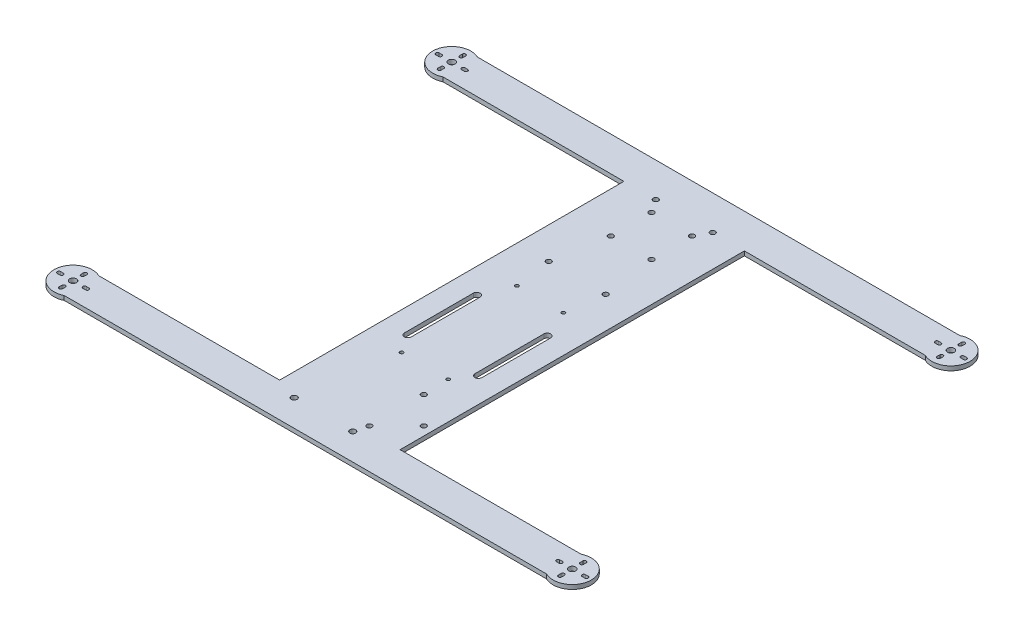
SolidWorks part; units mm, degrees
ref_plane "Front Plane" through (0, 0, 0) normal (0, 0, 1) x (1, 0, 0)
ref_plane "Top Plane" through (0, 0, 0) normal (0, 1, 0) x (1, 0, 0)
ref_plane "Right Plane" through (0, 0, 0) normal (1, 0, 0) x (0, 0, -1)
sketch "Sketch2" plane through (0, 0, 0) normal (0, 1, 0) x (1, 0, 0)
  line L0 (-44.45, 0) -> (44.45, 0) construction
  line L1 (-41.275, 152.4) -> (41.275, 152.4)
  line L2 (-44.45, 149.225) -> (-44.45, -149.225)
  line L3 (-41.275, -152.4) -> (41.275, -152.4)
  line L4 (44.45, 149.225) -> (44.45, -149.225)
  line L5 (0, 152.4) -> (0, -152.4) construction
  arc A0 (-44.45, -149.225) -> (-41.275, -152.4) centre (-41.275, -149.225) ccw
  arc A1 (41.275, -152.4) -> (44.45, -149.225) centre (41.275, -149.225) ccw
  arc A2 (41.275, 152.4) -> (44.45, 149.225) centre (41.275, 149.225) cw
  arc A3 (-41.275, 152.4) -> (-44.45, 149.225) centre (-41.275, 149.225) ccw
  point P8 (0, 0)
  point P13 (-44.45, -152.4)
  point P16 (44.45, -152.4)
  point P21 (-44.45, 152.4)
  dimension "D3" = 3.175
  dimension "D1" = 304.8
  dimension "D2" = 88.9
extrude "Plate Thickness" add sketch "Sketch2" along normal blind 3.175 contours L2 A0 L3 A1 L4 A2 L1 A3
sketch "Sketch10" plane through (0, 3.175, 0) normal (0, 1, 0) x (1, 0, 0)
  line L1 (41.275, 152.4) -> (177.986, 152.4)
  line L2 (41.275, 152.4) -> (41.275, 127)
  line L3 (41.275, 127) -> (177.986, 127)
  line L5 (44.45, 149.225) -> (44.45, -149.225) construction
  line L6 (0, 0) -> (0, 234.1968) construction
  line L7 (0, 0) -> (254.2756, 0) construction
  line L8 (41.275, -127) -> (177.986, -127)
  line L9 (41.275, -152.4) -> (41.275, -127)
  line L10 (41.275, -152.4) -> (177.986, -152.4)
  line L11 (41.275, 152.4) -> (177.986, 152.4)
  line L12 (41.275, 152.4) -> (41.275, 127)
  line L13 (41.275, 127) -> (177.986, 127)
  line L14 (41.275, -127) -> (177.986, -127)
  line L15 (41.275, -152.4) -> (41.275, -127)
  line L16 (41.275, -152.4) -> (177.986, -152.4)
  line L17 (41.275, 152.4) -> (177.986, 152.4)
  line L18 (41.275, 152.4) -> (41.275, 127)
  line L19 (41.275, 127) -> (177.986, 127)
  line L20 (41.275, -127) -> (177.986, -127)
  line L21 (41.275, -152.4) -> (41.275, -127)
  line L22 (41.275, -152.4) -> (177.986, -152.4)
  line L23 (41.275, 152.4) -> (177.986, 152.4)
  line L24 (41.275, 152.4) -> (41.275, 127)
  line L25 (41.275, 127) -> (177.986, 127)
  line L26 (41.275, -127) -> (177.986, -127)
  line L27 (41.275, -152.4) -> (41.275, -127)
  line L28 (41.275, -152.4) -> (177.986, -152.4)
  line L29 (-41.275, -127) -> (-177.986, -127)
  line L30 (-41.275, -152.4) -> (-41.275, -127)
  line L31 (-41.275, -152.4) -> (-177.986, -152.4)
  line L32 (-41.275, 127) -> (-177.986, 127)
  line L33 (-41.275, 152.4) -> (-41.275, 127)
  line L34 (-41.275, 152.4) -> (-177.986, 152.4)
  arc A0 (177.986, 127) -> (177.986, 152.4) centre (184.15, 139.7) ccw
  arc A1 (177.986, -127) -> (177.986, -152.4) centre (184.15, -139.7) cw
  arc A2 (177.986, 127) -> (177.986, 152.4) centre (184.15, 139.7) ccw
  arc A3 (177.986, -127) -> (177.986, -152.4) centre (184.15, -139.7) cw
  arc A4 (177.986, 127) -> (177.986, 152.4) centre (184.15, 139.7) ccw
  arc A5 (177.986, -127) -> (177.986, -152.4) centre (184.15, -139.7) cw
  arc A6 (177.986, 127) -> (177.986, 152.4) centre (184.15, 139.7) ccw
  arc A7 (177.986, -127) -> (177.986, -152.4) centre (184.15, -139.7) cw
  arc A8 (-177.986, -127) -> (-177.986, -152.4) centre (-184.15, -139.7) ccw
  arc A9 (-177.986, 127) -> (-177.986, 152.4) centre (-184.15, 139.7) cw
  point P27 (184.15, 134.2785)
  point P28 (0, 0)
  point P29 (0, 0)
  arc M45 (-41.275, 152.4) -> (-44.45, 149.225) centre (-41.275, 149.225) ccw
  line M46 (-44.45, 149.225) -> (-44.45, -149.225)
  arc M47 (-44.45, -149.225) -> (-41.275, -152.4) centre (-41.275, -149.225) ccw
  arc M49 (41.275, -152.4) -> (44.45, -149.225) centre (41.275, -149.225) ccw
  line M50 (44.45, -149.225) -> (44.45, 149.225)
  arc M51 (44.45, 149.225) -> (41.275, 152.4) centre (41.275, 149.225) ccw
  dimension "D1" = 139.7
  dimension "D2" = 25.4
extrude "Boss-Extrude1" add sketch "Sketch10" against normal up to surface (3.175 mm away) contours A9 L32 L34 M46 M45 | L3 A0 L1 M51 M50 | A1 L8 L10 M50 M49 | L29 A8 L31 M47 M46 region at (120.5918, 3.175, 139.7067) region at (120.5918, 3.175, -139.7067) region at (-120.5918, 3.175, -139.7067) region at (-120.5918, 3.175, 139.7067) up to face at (0, 0, 0)
sketch "Sketch3" plane through (0, 3.175, 0) normal (0, 1, 0) x (1, 0, 0)
  line L0 (-44.45, 127) -> (-44.45, -127) construction
  line L1 (-177.986, 152.4) -> (177.986, 152.4) construction
  line L4 (0, 152.4) -> (0, -152.4) construction
  line L5 (-177.986, -152.4) -> (177.986, -152.4) construction
  circle A0 centre (-38.1, 146.05) radius 2.159
  circle A1 centre (-38.1, 79.375) radius 2.159
  circle A2 centre (-38.1, -66.675) radius 2.159
  circle A3 centre (-38.1, -133.35) radius 2.159
  circle A4 centre (38.1, -133.35) radius 2.159
  circle A5 centre (38.1, -66.675) radius 2.159
  circle A6 centre (38.1, 79.375) radius 2.159
  circle A7 centre (38.1, 146.05) radius 2.159
  circle A8 centre (0, 146.05) radius 2.159
  circle A9 centre (0, -133.35) radius 2.159
  circle A10 centre (-38.1, 0) radius 2.159
  circle A11 centre (38.1, 0) radius 2.159
  dimension "D1" = 4.318
  dimension "D4" = 4.318
  dimension "D2" = 6.35
  dimension "D3" = 6.35
  dimension "D5" = 66.675
  dimension "D6" = 6.35
  dimension "D7" = 66.675
extrude "Mounting holes" [suppressed] cut sketch "Sketch3" against normal through all
sketch "Sketch4" plane through (0, 3.175, 0) normal (0, 1, 0) x (1, 0, 0)
  line L0 (-21.0058, 48.0812) -> (21.0058, 48.0812) construction
  line L1 (0, 0) -> (0, 139.7) construction
  circle A0 centre (-21.0058, 127.0752) radius 1.905
  circle A1 centre (-21.0058, 48.0812) radius 1.905
  circle A2 centre (21.0058, 48.0812) radius 1.905
  circle A3 centre (21.0058, 127.0752) radius 1.905
  point P13 (0, 48.0812)
  point P17 (0, 69.85)
  point P18 (0, 69.85)
  dimension "D1" = 3.81
  dimension "D2" = 78.994
  dimension "D3" = 42.0116
extrude "Jetson Holes (w/ mount)" cut sketch "Sketch4" against normal through all
sketch "Sketch5" plane through (0, 3.175, 0) normal (0, 1, 0) x (1, 0, 0)
  circle A1 centre (-14.3419, 117.2351) radius 1.905
  circle A3 centre (15.6555, 117.2351) radius 1.905
  circle A4 centre (15.6555, 87.2377) radius 1.905
  circle A5 centre (-14.3419, 87.2377) radius 1.905
  dimension "D1" = 3.81
  dimension "D2" = 29.9974
  dimension "D3" = 29.9974
extrude "PDB holes" cut sketch "Sketch5" against normal through all
sketch "Sketch6" plane through (0, 3.175, 0) normal (0, 1, 0) x (1, 0, 0)
  circle A6 centre (38.0032, -103.0828) radius 1.905
  circle A7 centre (17.9372, -83.0168) radius 1.905
  circle A8 centre (17.9372, -123.1488) radius 1.905
  dimension "D5" = 3.81
  dimension "D6" = 40.132
  dimension "D7" = 20.066
  dimension "D8" = 20.066
extrude "Lidar Holes" cut sketch "Sketch6" against normal through all
sketch "Sketch7" plane through (0, 3.175, 0) normal (0, 1, 0) x (1, 0, 0)
  line L0 (0, 152.4) -> (0, -152.4) construction
  line L1 (-177.986, 152.4) -> (177.986, 152.4) construction
  line L2 (-177.986, -152.4) -> (177.986, -152.4) construction
  line L3 (17.145, 20.7699) -> (-17.145, 20.7699) construction
  circle A0 centre (-17.145, 20.7699) radius 1.27
  circle A1 centre (-17.145, -64.3201) radius 1.27
  circle A2 centre (17.145, -64.3201) radius 1.27
  circle A3 centre (17.145, 20.7699) radius 1.27
  point P14 (0, 20.7699)
  dimension "D1" = 2.54
  dimension "D2" = 85.09
  dimension "D3" = 34.29
extrude "PixHawk Holes" cut sketch "Sketch7" against normal through all
sketch "Sketch8" plane through (0, 3.175, 0) normal (0, 1, 0) x (1, 0, 0)
  line L0 (0, 152.4) -> (0, -115.5095) construction
  line L1 (-177.986, 152.4) -> (177.986, 152.4) construction
  line L2 (-26.035, -0.006) -> (-26.035, -50.806) construction
  line L3 (-23.495, -0.006) -> (-23.495, -50.806)
  line L4 (-28.575, -0.006) -> (-28.575, -50.806)
  line L5 (26.035, -0.006) -> (26.035, -50.806) construction
  line L6 (23.495, -0.006) -> (23.495, -50.806)
  line L7 (28.575, -0.006) -> (28.575, -50.806)
  arc A0 (-23.495, -0.006) -> (-28.575, -0.006) centre (-26.035, -0.006) ccw
  arc A1 (-28.575, -50.806) -> (-23.495, -50.806) centre (-26.035, -50.806) ccw
  arc A2 (23.495, -0.006) -> (28.575, -0.006) centre (26.035, -0.006) cw
  arc A3 (28.575, -50.806) -> (23.495, -50.806) centre (26.035, -50.806) cw
  point P7 (-26.035, -25.406)
  point P14 (26.035, -25.406)
  dimension "D1" = 50.8
  dimension "D2" = 5.08
  dimension "D3" = 26.035
extrude "Battery Holes" cut sketch "Sketch8" against normal through all
sketch "Sketch9" plane through (0, 3.175, 0) normal (0, 1, 0) x (1, 0, 0)
  circle A0 centre (-27.8687, -132.8308) radius 2.159
  circle A1 centre (15.3113, -132.8308) radius 2.159
  dimension "D1" = 4.318
  dimension "D2" = 4.318
  dimension "D3" = 43.18
extrude "Cut-Extrude1" cut sketch "Sketch9" against normal through all
sketch "Sketch11" plane through (0, 3.175, 0) normal (0, 1, 0) x (1, 0, 0)
  line L0 (173.65, 139.7) -> (175.65, 139.7) construction
  line L1 (173.65, 140.95) -> (175.65, 140.95)
  line L2 (173.65, 138.45) -> (175.65, 138.45)
  line L3 (184.15, 139.7) -> (184.15, 143.0164) construction
  line L4 (194.65, 139.7) -> (192.65, 139.7) construction
  line L5 (194.65, 140.95) -> (192.65, 140.95)
  line L6 (194.65, 138.45) -> (192.65, 138.45)
  line L7 (184.15, 148.7) -> (184.15, 146.7) construction
  line L8 (185.4, 148.7) -> (185.4, 146.7)
  line L9 (182.9, 148.7) -> (182.9, 146.7)
  line L10 (184.15, 139.7) -> (199.8184, 139.7) construction
  line L11 (184.15, 130.7) -> (184.15, 132.7) construction
  line L12 (185.4, 130.7) -> (185.4, 132.7)
  line L13 (182.9, 130.7) -> (182.9, 132.7)
  line L14 (44.45, 127) -> (44.45, -127) construction
  line L15 (-177.986, 152.4) -> (177.986, 152.4) construction
  line L16 (0, 0) -> (0, 273.2731) construction
  line L19 (0, 0) -> (202.4297, 0) construction
  line L22 (184.15, -139.7) -> (199.8184, -139.7) construction
  line L25 (184.15, -139.7) -> (184.15, -143.0164) construction
  line L28 (184.15, -130.7) -> (184.15, -132.7) construction
  line L29 (185.4, -130.7) -> (185.4, -132.7)
  line L30 (182.9, -130.7) -> (182.9, -132.7)
  line L33 (184.15, -148.7) -> (184.15, -146.7) construction
  line L36 (185.4, -148.7) -> (185.4, -146.7)
  line L39 (182.9, -148.7) -> (182.9, -146.7)
  line L42 (194.65, -139.7) -> (192.65, -139.7) construction
  line L43 (194.65, -140.95) -> (192.65, -140.95)
  line L44 (194.65, -138.45) -> (192.65, -138.45)
  line L45 (173.65, -139.7) -> (175.65, -139.7) construction
  line L46 (173.65, -140.95) -> (175.65, -140.95)
  line L49 (173.65, -138.45) -> (175.65, -138.45)
  line L52 (-184.15, -139.7) -> (-184.15, -143.0164) construction
  line L55 (-184.15, -139.7) -> (-199.8184, -139.7) construction
  line L58 (-173.65, -139.7) -> (-175.65, -139.7) construction
  line L59 (-173.65, -140.95) -> (-175.65, -140.95)
  line L60 (-173.65, -138.45) -> (-175.65, -138.45)
  line L61 (-184.15, -148.7) -> (-184.15, -146.7) construction
  line L62 (-185.4, -148.7) -> (-185.4, -146.7)
  line L63 (-182.9, -148.7) -> (-182.9, -146.7)
  line L64 (-184.15, -130.7) -> (-184.15, -132.7) construction
  line L65 (-185.4, -130.7) -> (-185.4, -132.7)
  line L66 (-182.9, -130.7) -> (-182.9, -132.7)
  line L67 (-194.65, -139.7) -> (-192.65, -139.7) construction
  line L68 (-194.65, -140.95) -> (-192.65, -140.95)
  line L69 (-194.65, -138.45) -> (-192.65, -138.45)
  line L70 (-184.15, 139.7) -> (-199.8184, 139.7) construction
  line L71 (-184.15, 139.7) -> (-184.15, 143.0164) construction
  line L72 (-184.15, 130.7) -> (-184.15, 132.7) construction
  line L73 (-185.4, 130.7) -> (-185.4, 132.7)
  line L74 (-182.9, 130.7) -> (-182.9, 132.7)
  line L75 (-184.15, 148.7) -> (-184.15, 146.7) construction
  line L76 (-185.4, 148.7) -> (-185.4, 146.7)
  line L77 (-182.9, 148.7) -> (-182.9, 146.7)
  line L78 (-194.65, 139.7) -> (-192.65, 139.7) construction
  line L79 (-194.65, 140.95) -> (-192.65, 140.95)
  line L80 (-194.65, 138.45) -> (-192.65, 138.45)
  line L81 (-173.65, 139.7) -> (-175.65, 139.7) construction
  line L82 (-173.65, 140.95) -> (-175.65, 140.95)
  line L83 (-173.65, 138.45) -> (-175.65, 138.45)
  circle A0 centre (184.15, 139.7) radius 2.5
  arc A1 (173.65, 140.95) -> (173.65, 138.45) centre (173.65, 139.7) ccw
  arc A2 (175.65, 138.45) -> (175.65, 140.95) centre (175.65, 139.7) ccw
  arc A4 (194.65, 140.95) -> (194.65, 138.45) centre (194.65, 139.7) cw
  arc A5 (192.65, 138.45) -> (192.65, 140.95) centre (192.65, 139.7) cw
  arc A6 (185.4, 148.7) -> (182.9, 148.7) centre (184.15, 148.7) ccw
  arc A7 (182.9, 146.7) -> (185.4, 146.7) centre (184.15, 146.7) ccw
  arc A8 (185.4, 130.7) -> (182.9, 130.7) centre (184.15, 130.7) cw
  arc A9 (182.9, 132.7) -> (185.4, 132.7) centre (184.15, 132.7) cw
  circle A37 centre (184.15, -139.7) radius 2.5
  arc A38 (185.4, -130.7) -> (182.9, -130.7) centre (184.15, -130.7) ccw
  arc A39 (182.9, -132.7) -> (185.4, -132.7) centre (184.15, -132.7) ccw
  arc A40 (185.4, -148.7) -> (182.9, -148.7) centre (184.15, -148.7) cw
  arc A41 (182.9, -146.7) -> (185.4, -146.7) centre (184.15, -146.7) cw
  arc A42 (194.65, -140.95) -> (194.65, -138.45) centre (194.65, -139.7) ccw
  arc A43 (192.65, -138.45) -> (192.65, -140.95) centre (192.65, -139.7) ccw
  arc A44 (173.65, -140.95) -> (173.65, -138.45) centre (173.65, -139.7) cw
  arc A45 (175.65, -138.45) -> (175.65, -140.95) centre (175.65, -139.7) cw
  circle A46 centre (-184.15, -139.7) radius 2.5
  arc A47 (-173.65, -140.95) -> (-173.65, -138.45) centre (-173.65, -139.7) ccw
  arc A48 (-175.65, -138.45) -> (-175.65, -140.95) centre (-175.65, -139.7) ccw
  arc A49 (-185.4, -148.7) -> (-182.9, -148.7) centre (-184.15, -148.7) ccw
  arc A50 (-182.9, -146.7) -> (-185.4, -146.7) centre (-184.15, -146.7) ccw
  arc A51 (-185.4, -130.7) -> (-182.9, -130.7) centre (-184.15, -130.7) cw
  arc A52 (-182.9, -132.7) -> (-185.4, -132.7) centre (-184.15, -132.7) cw
  arc A53 (-194.65, -140.95) -> (-194.65, -138.45) centre (-194.65, -139.7) cw
  arc A54 (-192.65, -138.45) -> (-192.65, -140.95) centre (-192.65, -139.7) cw
  circle A55 centre (-184.15, 139.7) radius 2.5
  arc A56 (-185.4, 130.7) -> (-182.9, 130.7) centre (-184.15, 130.7) ccw
  arc A57 (-182.9, 132.7) -> (-185.4, 132.7) centre (-184.15, 132.7) ccw
  arc A58 (-185.4, 148.7) -> (-182.9, 148.7) centre (-184.15, 148.7) cw
  arc A59 (-182.9, 146.7) -> (-185.4, 146.7) centre (-184.15, 146.7) cw
  arc A60 (-194.65, 140.95) -> (-194.65, 138.45) centre (-194.65, 139.7) ccw
  arc A61 (-192.65, 138.45) -> (-192.65, 140.95) centre (-192.65, 139.7) ccw
  arc A62 (-173.65, 140.95) -> (-173.65, 138.45) centre (-173.65, 139.7) cw
  arc A63 (-175.65, 138.45) -> (-175.65, 140.95) centre (-175.65, 139.7) cw
  point P5 (174.65, 139.7)
  point P16 (193.65, 139.7)
  point P23 (184.15, 147.7)
  point P31 (184.15, 131.7)
  point P47 (184.15, -131.7)
  point P54 (184.15, -147.7)
  point P61 (193.65, -139.7)
  point P68 (174.65, -139.7)
  point P79 (-174.65, -139.7)
  point P86 (-184.15, -147.7)
  point P93 (-184.15, -131.7)
  point P100 (-193.65, -139.7)
  point P111 (-184.15, 131.7)
  point P118 (-184.15, 147.7)
  point P125 (-193.65, 139.7)
  point P132 (-174.65, 139.7)
  dimension "D1" = 5
  dimension "D2" = 2.5
  dimension "D3" = 2
  dimension "D4" = 19
  dimension "D5" = 2.5
  dimension "D6" = 2
  dimension "D7" = 16
  dimension "D8" = 139.7
  dimension "D9" = 12.7
extrude "Cut-Extrude2" cut sketch "Sketch11" against normal through all
